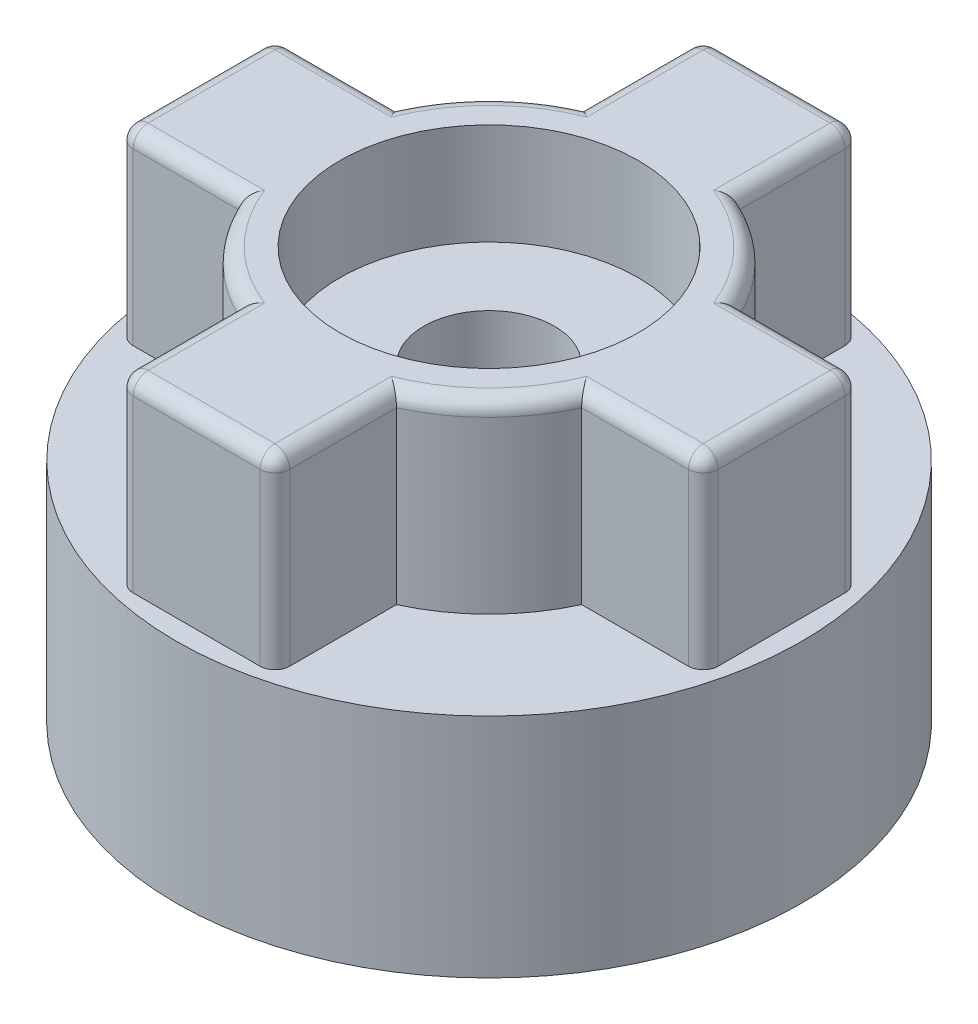
SolidWorks part; units mm, degrees
material "ABS PC"
ref_plane "Front Plane" through (0, 0, 0) normal (0, 0, 1) x (1, 0, 0)
ref_plane "Top Plane" through (0, 0, 0) normal (0, 1, 0) x (1, 0, 0)
ref_plane "Right Plane" through (0, 0, 0) normal (1, 0, 0) x (0, 0, -1)
sketch "Sketch1" plane through (0, 0, 0) normal (0, 1, 0) x (1, 0, 0)
  circle A0 centre (0, 0) radius 26.6192
  dimension "D1" = 53.2384
extrude "Boss-Extrude1" add sketch "Sketch1" along normal blind 19.304
sketch "Sketch2" plane through (0, 19.304, 0) normal (0, 1, 0) x (1, 0, 0)
  line L0 (-6.6675, 14.5468) -> (-6.6675, 24.892)
  line L1 (-6.6675, -24.892) -> (6.6675, -24.892)
  line L2 (-6.6675, -24.892) -> (-6.6675, -14.5468)
  line L3 (-6.6675, 24.892) -> (6.6675, 24.892)
  line L4 (6.6675, -24.892) -> (6.6675, -14.5468)
  line L5 (-6.6675, -24.892) -> (6.6675, 24.892) construction
  line L6 (-6.6675, 24.892) -> (6.6675, -24.892) construction
  line L7 (-24.892, -6.6675) -> (-14.5468, -6.6675)
  line L8 (-24.892, -6.6675) -> (-24.892, 6.6675)
  line L9 (-24.892, 6.6675) -> (-14.5468, 6.6675)
  line L10 (24.892, -6.6675) -> (24.892, 6.6675)
  line L11 (-24.892, -6.6675) -> (24.892, 6.6675) construction
  line L12 (-24.892, 6.6675) -> (24.892, -6.6675) construction
  line L13 (6.6675, 14.5468) -> (6.6675, 24.892)
  line L14 (14.5468, -6.6675) -> (24.892, -6.6675)
  line L15 (14.5468, 6.6675) -> (24.892, 6.6675)
  arc A0 (-6.6675, 14.5468) -> (-14.5468, 6.6675) centre (0, 0) ccw
  arc A1 (-14.5468, -6.6675) -> (-6.6675, -14.5468) centre (0, 0) ccw
  arc A2 (6.6675, -14.5468) -> (14.5468, -6.6675) centre (0, 0) ccw
  arc A3 (14.5468, 6.6675) -> (6.6675, 14.5468) centre (0, 0) ccw
  dimension "D1" = 32.004
  dimension "D2" = 49.784
  dimension "D3" = 13.335
extrude "Boss-Extrude2" add sketch "Sketch2" along normal blind 15.7734
sketch "Sketch3" plane through (0, 35.0774, 0) normal (0, 1, 0) x (1, 0, 0)
  circle A0 centre (0, 0) radius 12.7
  dimension "D1" = 25.4
extrude "Cut-Extrude1" cut sketch "Sketch3" against normal blind 8.636
sketch "Sketch4" plane through (0, 26.4414, 0) normal (0, 1, 0) x (1, 0, 0)
  circle A0 centre (0, 0) radius 5.5562
  dimension "D1" = 11.1125
extrude "Cut-Extrude2" cut sketch "Sketch4" against normal through all
fillet "Fillet1" radius 1.27 16 edges at (-11.3151, 35.0774, 11.3151) (-6.6675, 35.0774, 19.7194) (0, 35.0774, 24.892) (6.6675, 35.0774, 19.7194) (11.3151, 35.0774, 11.3151) (19.7194, 35.0774, 6.6675) (24.892, 35.0774, 0) (19.7194, 35.0774, -6.6675) (11.3151, 35.0774, -11.3151) (6.6675, 35.0774, -19.7194) (-6.6675, 35.0774, -19.7194) (0, 35.0774, -24.892) (-11.3151, 35.0774, -11.3151) (-19.7194, 35.0774, -6.6675) (-24.892, 35.0774, 0) (-19.7194, 35.0774, 6.6675)
fillet "Fillet2" radius 1.27 16 edges at (-24.52, 34.7054, -6.2955) (-6.2955, 34.7054, -24.52) (6.2955, 34.7054, -24.52) (24.52, 34.7054, -6.2955) (24.52, 34.7054, 6.2955) (6.2955, 34.7054, 24.52) (-6.2955, 34.7054, 24.52) (-24.52, 34.7054, 6.2955) (-24.892, 26.5557, -6.6675) (-6.6675, 26.5557, -24.892) (6.6675, 26.5557, -24.892) (24.892, 26.5557, -6.6675) (24.892, 26.5557, 6.6675) (6.6675, 26.5557, 24.892) (-6.6675, 26.5557, 24.892) (-24.892, 26.5557, 6.6675)
